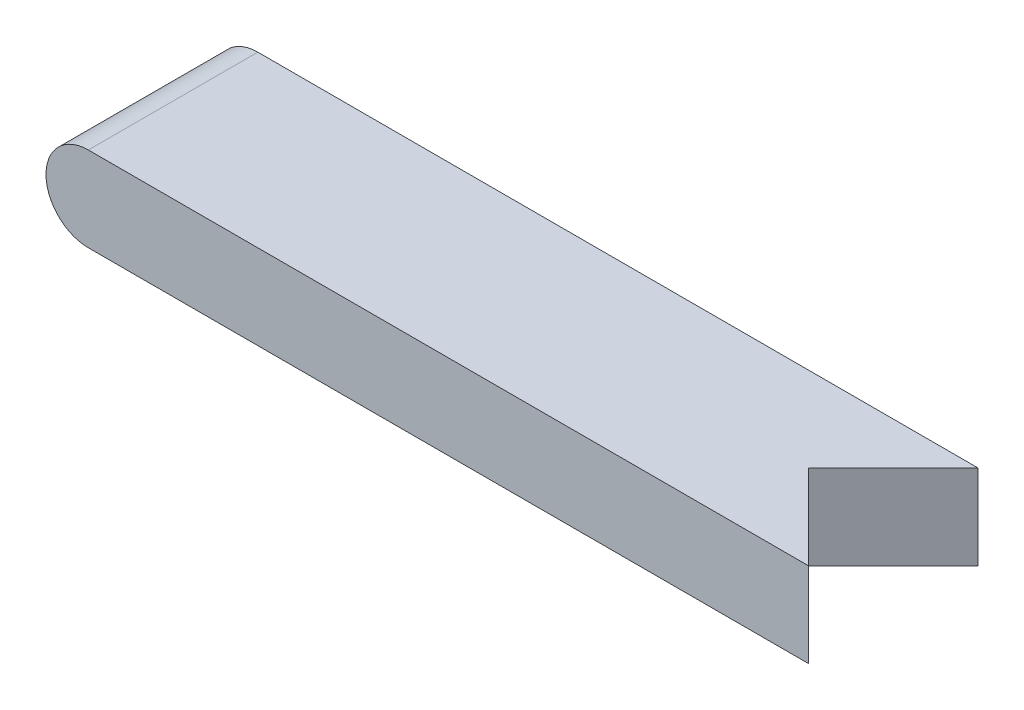
SolidWorks part; units mm, degrees
ref_plane "Front Plane" through (0, 0, 0) normal (0, 0, 1) x (1, 0, 0)
ref_plane "Top Plane" through (0, 0, 0) normal (0, 1, 0) x (1, 0, 0)
ref_plane "Right Plane" through (0, 0, 0) normal (1, 0, 0) x (0, 0, -1)
sketch "Sketch1" plane through (0, 0, 0) normal (0, 1, 0) x (1, 0, 0)
  line L0 (12.7, 0) -> (0, 0)
  line L1 (12.7, 5.08) -> (-10.16, 5.08)
  line L2 (12.7, 0) -> (12.7, 5.08)
  line L3 (-10.16, 5.08) -> (-10.16, 0)
  line L4 (-10.16, 0) -> (0, 0)
extrude "Boss-Extrude1" add sketch "Sketch1" along normal blind 2.54
fillet "Fillet1" radius 1.27 2 edges at (-10.16, 0, -2.54) (-10.16, 2.54, -2.54)
sketch "Sketch3" plane through (0, 2.54, 0) normal (0, 1, 0) x (1, 0, 0)
  line L1 (12.7, 5.08) -> (10.16, 2.54)
  line L2 (10.16, 2.54) -> (12.7, 0)
  line L3 (12.7, 0) -> (12.7, 5.08)
extrude "Cut-Extrude2" cut sketch "Sketch3" against normal blind 2.54
